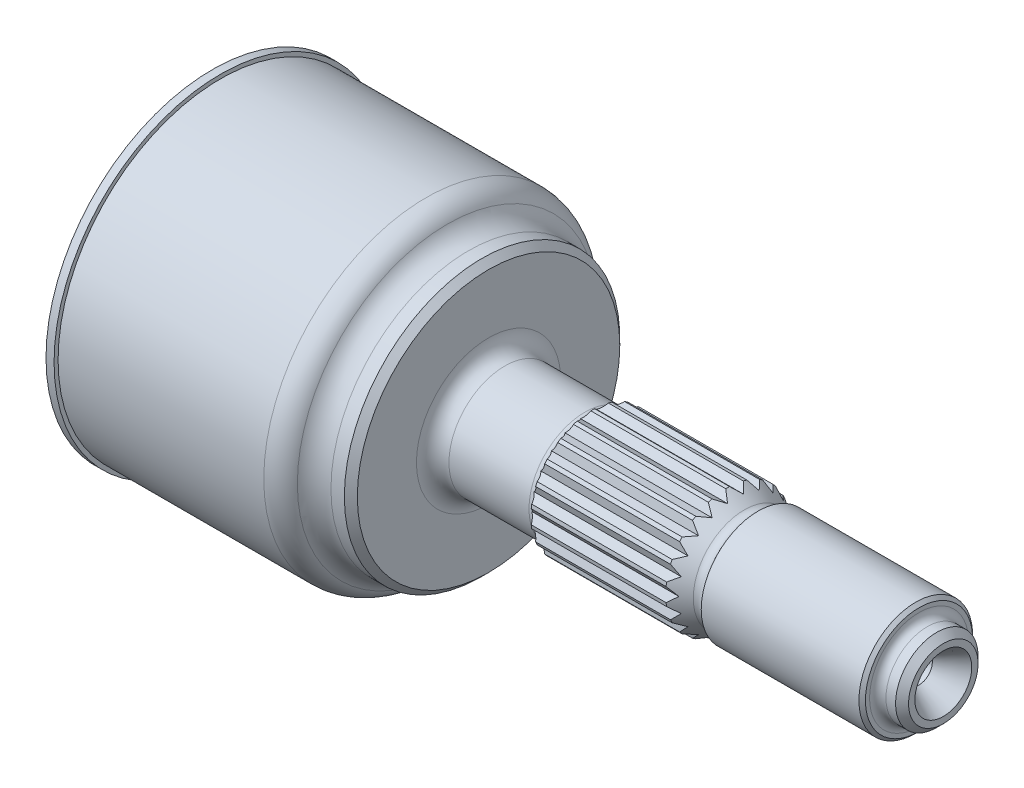
SolidWorks part; units mm, degrees
material "AISI 4340 Steel, normalized"
ref_plane "Front-XY" through (0, 0, 0) normal (0, 0, 1) x (1, 0, 0)
ref_plane "Top-XZ" through (0, 0, 0) normal (0, 1, 0) x (1, 0, 0)
ref_plane "Right-YZ" through (0, 0, 0) normal (1, 0, 0) x (0, 0, -1)
sketch "Sketch1" plane through (0, 0, 0) normal (0, 1, 0) x (1, 0, 0)
  line L0 (0, 0) -> (0, 32.5374)
  line L1 (0, 32.5374) -> (1.5748, 32.5374)
  line L2 (1.5748, 32.5374) -> (1.5748, 31.75)
  line L3 (1.5748, 31.75) -> (41.783, 31.75)
  line L4 (100.711, 12.1031) -> (103.9797, 9.9804)
  line L5 (50.0888, 26.924) -> (52.705, 26.924)
  line L6 (53.975, 25.654) -> (53.975, 14.097)
  line L7 (57.15, 10.922) -> (72.7964, 10.922)
  line L8 (74.3407, 12.1031) -> (100.711, 12.1031)
  line L9 (-31.2881, 0) -> (113.4065, 0) construction
  line L10 (52.705, 26.924) -> (53.975, 25.654)
  line L11 (106.6636, 11.1125) -> (106.1569, 10.3974)
  line L12 (106.6636, 11.1125) -> (137.4902, 11.1125)
  line L13 (138.1252, 10.4775) -> (138.1252, 9.6647)
  line L14 (139.7254, 8.0645) -> (141.605, 8.0645)
  line L15 (142.875, 6.7945) -> (142.875, 5.5626)
  line L16 (142.875, 5.5626) -> (138.1252, 2.6099)
  line L17 (138.1252, 2.6099) -> (134.3152, 2.6098)
  line L18 (134.3152, 2.6098) -> (132.5548, 0)
  line L19 (132.5548, 0) -> (0, 0)
  line L20 (141.605, 8.0645) -> (142.875, 6.7945)
  line L21 (137.4902, 11.1125) -> (138.1252, 10.4775)
  arc A0 (41.783, 31.75) -> (45.9359, 29.337) centre (41.783, 26.9698) cw
  arc A1 (45.9359, 29.337) -> (50.0888, 26.924) centre (50.0888, 31.7042) ccw
  arc A2 (53.975, 14.097) -> (57.15, 10.922) centre (57.15, 14.097) ccw
  arc A3 (72.7964, 10.922) -> (74.3407, 12.1031) centre (72.7964, 12.5222) ccw
  arc A4 (138.1252, 9.6647) -> (139.7254, 8.0645) centre (139.7254, 9.6647) ccw
  arc A5 (103.9797, 9.9804) -> (106.1569, 10.3974) centre (104.8512, 11.3224) ccw
  point P7 (53.975, 26.924)
  point P25 (138.1252, 11.1125)
  point P27 (142.875, 8.0645)
  point P35 (138.1252, 8.0645)
  dimension "D1" = 31.75
  dimension "D8" = 50.0888
  dimension "D10" = 3.175
  dimension "D11" = 1.6002
  dimension "D28" = 1.6002
  dimension "D16" = 1.6002
  dimension "D2" = 26.924
  dimension "D3" = 53.975
  dimension "D4" = 1.5748
  dimension "D5" = 32.5374
  dimension "D6" = 1.27
  dimension "D7" = 45
  dimension "D9" = 41.783
  dimension "D12" = 72.7964
  dimension "D13" = 10.922
  dimension "D14" = 12.1031
  dimension "D15" = 100.711
  dimension "D17" = 33
  dimension "D18" = 8.0645
  dimension "D19" = 142.875
  dimension "D20" = 138.1252
  dimension "D21" = 11.1125
  dimension "D22" = 5.5626
  dimension "D23" = 1.27
  dimension "D24" = 45
  dimension "D25" = 56
  dimension "D26" = 2.6098
  dimension "D27" = 3.81
  dimension "D29" = 104.8512
  dimension "D30" = 0.5067
revolve "ProfileRevolve" add sketch "Sketch1" angle 360 about L9
cosmetic thread "Cosmetic Thread1" parameters "D2"=19.304
sketch "Sketch2" plane through (0, 0, 0) normal (-1, 0, 0) x (0, 0, 1)
  circle A0 centre (0, 0) radius 18.2245
  dimension "D1" = 36.449
extrude "CenterPocket" cut sketch "Sketch2" against normal blind 43.942
sketch "Sketch4" plane through (0, 0, 0) normal (-1, 0, 0) x (0, 0, 1)
  circle A0 centre (0, 24.638) radius 4.7625
  circle A1 centre (21.3371, -12.319) radius 4.7625
  circle A2 centre (-21.3371, -12.319) radius 4.7625
  dimension "D1" = 9.525
  dimension "D2" = 24.638
extrude "Holes" cut sketch "Sketch4" against normal blind 41.275
sketch "Sketch5" plane through (0, 0, 0) normal (-1, 0, 0) x (0, 0, 1)
  arc A0 (-9.9429, -27.1954) -> (9.9429, -27.1954) centre (0, 0) ccw
  circle A1 centre (0, 0) radius 20.32 construction
  arc A2 (11.7591, -25.4916) -> (-11.7591, -25.4916) centre (0, -20.32) ccw
  arc A3 (-27.9559, 2.5622) -> (-16.1969, 22.9294) centre (-17.5976, 10.16) ccw
  arc A4 (-18.5804, 22.2085) -> (-28.5233, 4.9868) centre (0, 0) ccw
  arc A5 (16.1969, 22.9294) -> (27.9559, 2.5622) centre (17.5976, 10.16) ccw
  arc A6 (28.5233, 4.9868) -> (18.5804, 22.2085) centre (0, 0) ccw
  arc A7 (11.7591, -25.4916) -> (9.9429, -27.1954) centre (8.8527, -24.2134) cw
  arc A8 (-11.7591, -25.4916) -> (-9.9429, -27.1954) centre (-8.8527, -24.2134) ccw
  arc A9 (27.9559, 2.5622) -> (28.5233, 4.9868) centre (25.3958, 4.44) ccw
  arc A10 (16.1969, 22.9294) -> (18.5804, 22.2085) centre (16.5431, 19.7734) cw
  arc A11 (-16.1969, 22.9294) -> (-18.5804, 22.2085) centre (-16.5431, 19.7734) ccw
  arc A12 (-27.9559, 2.5622) -> (-28.5233, 4.9868) centre (-25.3958, 4.44) cw
  dimension "D1" = 57.912
  dimension "D2" = 40.64
  dimension "D3" = 25.6921
  dimension "D4" = 3.175
extrude "Extrude3" cut sketch "Sketch5" against normal blind 43.942
sketch "Sketch6" plane through (0, 0, 0) normal (0, 0, 1) x (1, 0, 0)
  line L0 (43.922, 18.2245) -> (2.9156, 18.2245)
  line L1 (-21.4392, 0) -> (31.2558, 0) construction
  line L3 (-4.0132, 0) -> (50.8508, 0)
  arc A0 (2.9156, 18.2245) -> (-4.0132, 0) centre (23.4188, 0) ccw
  arc A1 (50.8508, 0) -> (43.922, 18.2245) centre (23.4188, 0) ccw
  dimension "D1" = 54.864
  dimension "D2" = 23.4188
  dimension "D3" = 18.2245
revolve "Cut-Revolve1" cut sketch "Sketch6" angle 360 about L1
ref_plane "Plane1" through (72.7964, 0, 0) normal (1, 0, 0) x (0, 0, -1)
sketch "Sketch7" plane through (72.7964, 0, 0) normal (1, 0, 0) x (0, 0, -1)
  line L0 (0, 12.1031) -> (1.5771, 10.9692) construction
  line L1 (1.5771, 10.9692) -> (3.4098, 11.6128) construction
  line L2 (0.3686, 12.0975) -> (1.5771, 10.9692)
  line L3 (1.5771, 10.9692) -> (3.0546, 11.7113)
  line L4 (0, 12.1031) -> (0.3686, 12.0975) construction
  line L5 (3.0546, 11.7113) -> (3.4098, 11.6128) construction
  line L6 (3.7619, 11.5036) -> (4.6036, 10.0805)
  line L7 (4.6036, 10.0805) -> (6.2303, 10.3763)
  line L8 (6.8505, 9.9778) -> (7.2571, 8.3752)
  line L9 (7.2571, 8.3752) -> (8.9013, 8.2007)
  line L10 (9.384, 7.6436) -> (9.3227, 5.9914)
  line L11 (9.3227, 5.9914) -> (10.8512, 5.3607)
  line L12 (11.1574, 4.6902) -> (10.6331, 3.1221)
  line L13 (10.6331, 3.1221) -> (11.9219, 2.0865)
  line L14 (12.0268, 1.3568) -> (11.082, 0)
  line L15 (11.082, 0) -> (12.0268, -1.3568)
  line L16 (11.9219, -2.0865) -> (10.6331, -3.1221)
  line L17 (10.6331, -3.1221) -> (11.1574, -4.6902)
  line L18 (10.8512, -5.3607) -> (9.3227, -5.9914)
  line L19 (9.3227, -5.9914) -> (9.384, -7.6436)
  line L20 (8.9013, -8.2007) -> (7.2571, -8.3752)
  line L21 (7.2571, -8.3752) -> (6.8505, -9.9778)
  line L22 (6.2303, -10.3763) -> (4.6036, -10.0805)
  line L23 (4.6036, -10.0805) -> (3.7619, -11.5036)
  line L24 (3.0546, -11.7113) -> (1.5771, -10.9692)
  line L25 (1.5771, -10.9692) -> (0.3686, -12.0975)
  line L26 (-0.3686, -12.0975) -> (-1.5771, -10.9692)
  line L27 (-1.5771, -10.9692) -> (-3.0546, -11.7113)
  line L28 (-3.7619, -11.5036) -> (-4.6036, -10.0805)
  line L29 (-4.6036, -10.0805) -> (-6.2303, -10.3763)
  line L30 (-6.8505, -9.9778) -> (-7.2571, -8.3752)
  line L31 (-7.2571, -8.3752) -> (-8.9013, -8.2007)
  line L32 (-9.384, -7.6436) -> (-9.3227, -5.9914)
  line L33 (-9.3227, -5.9914) -> (-10.8512, -5.3607)
  line L34 (-11.1574, -4.6902) -> (-10.6331, -3.1221)
  line L35 (-10.6331, -3.1221) -> (-11.9219, -2.0865)
  line L36 (-12.0268, -1.3568) -> (-11.082, 0)
  line L37 (-11.082, 0) -> (-12.0268, 1.3568)
  line L38 (-11.9219, 2.0865) -> (-10.6331, 3.1221)
  line L39 (-10.6331, 3.1221) -> (-11.1574, 4.6902)
  line L40 (-10.8512, 5.3607) -> (-9.3227, 5.9914)
  line L41 (-9.3227, 5.9914) -> (-9.384, 7.6436)
  line L42 (-8.9013, 8.2007) -> (-7.2571, 8.3752)
  line L43 (-7.2571, 8.3752) -> (-6.8505, 9.9778)
  line L44 (-6.2303, 10.3763) -> (-4.6036, 10.0805)
  line L45 (-4.6036, 10.0805) -> (-3.7619, 11.5036)
  line L46 (-3.0546, 11.7113) -> (-1.5771, 10.9692)
  line L47 (-1.5771, 10.9692) -> (-0.3686, 12.0975)
  circle A1 centre (0, 0) radius 12.1031 construction
  arc A2 (3.0546, 11.7113) -> (0.3686, 12.0975) centre (0, 0) ccw
  arc A3 (6.2303, 10.3763) -> (3.7619, 11.5036) centre (0, 0) ccw
  arc A4 (8.9013, 8.2007) -> (6.8505, 9.9778) centre (0, 0) ccw
  arc A5 (10.8512, 5.3607) -> (9.384, 7.6436) centre (0, 0) ccw
  arc A6 (11.9219, 2.0865) -> (11.1574, 4.6902) centre (0, 0) ccw
  arc A7 (12.0268, -1.3568) -> (12.0268, 1.3568) centre (0, 0) ccw
  arc A8 (11.1574, -4.6902) -> (11.9219, -2.0865) centre (0, 0) ccw
  arc A9 (9.384, -7.6436) -> (10.8512, -5.3607) centre (0, 0) ccw
  arc A10 (6.8505, -9.9778) -> (8.9013, -8.2007) centre (0, 0) ccw
  arc A11 (3.7619, -11.5036) -> (6.2303, -10.3763) centre (0, 0) ccw
  arc A12 (0.3686, -12.0975) -> (3.0546, -11.7113) centre (0, 0) ccw
  arc A13 (-3.0546, -11.7113) -> (-0.3686, -12.0975) centre (0, 0) ccw
  arc A14 (-6.2303, -10.3763) -> (-3.7619, -11.5036) centre (0, 0) ccw
  arc A15 (-8.9013, -8.2007) -> (-6.8505, -9.9778) centre (0, 0) ccw
  arc A16 (-10.8512, -5.3607) -> (-9.384, -7.6436) centre (0, 0) ccw
  arc A17 (-11.9219, -2.0865) -> (-11.1574, -4.6902) centre (0, 0) ccw
  arc A18 (-12.0268, 1.3568) -> (-12.0268, -1.3568) centre (0, 0) ccw
  arc A19 (-11.1574, 4.6902) -> (-11.9219, 2.0865) centre (0, 0) ccw
  arc A20 (-9.384, 7.6436) -> (-10.8512, 5.3607) centre (0, 0) ccw
  arc A21 (-6.8505, 9.9778) -> (-8.9013, 8.2007) centre (0, 0) ccw
  arc A22 (-3.7619, 11.5036) -> (-6.2303, 10.3763) centre (0, 0) ccw
  arc A23 (-0.3686, 12.0975) -> (-3.0546, 11.7113) centre (0, 0) ccw
  point P0 (-11.0094, 5.0278)
  point P1 (-11.9799, 1.7225)
  point P3 (0, 12.1031)
  point P8 (6.5434, -10.1818)
  point P9 (3.4098, 11.6128)
  point P10 (-11.9799, -1.7225)
  point P11 (6.5434, 10.1818)
  point P12 (9.1469, 7.9258)
  point P13 (11.0094, 5.0278)
  point P14 (11.9799, 1.7225)
  point P15 (11.9799, -1.7225)
  point P16 (11.0094, -5.0278)
  point P17 (9.1469, -7.9258)
  point P18 (-3.4098, 11.6128)
  point P19 (3.4098, -11.6128)
  point P20 (0, -12.1031)
  point P21 (-3.4098, -11.6128)
  point P22 (-6.5434, -10.1818)
  point P23 (-9.1469, -7.9258)
  point P24 (-11.0094, -5.0278)
  point P25 (-6.5434, 10.1818)
  point P26 (-9.1469, 7.9258)
  dimension "D1" = 0.3686
  dimension "D2" = 3.4098
extrude "Extrude4" cut sketch "Sketch7" along normal up to next
sketch "Sketch10" plane through (0, 0, 0) normal (0, 1, 0) x (1, 0, 0)
  line L0 (106.6636, 11.1125) -> (107.4335, 9.779)
  line L1 (0, 0) -> (202.1127, 0) construction
  line L2 (106.6636, -11.1125) -> (106.6636, 11.1125) construction
  line L3 (107.4335, 9.779) -> (108.2034, 11.1125)
  line L4 (137.4902, 11.1125) -> (106.6636, 11.1125) construction
  line L5 (108.2034, 11.1125) -> (106.6636, 11.1125)
  line L6 (109.2478, 9.779) -> (110.0177, 11.1125)
  line L7 (110.0177, 11.1125) -> (108.4779, 11.1125)
  line L8 (108.4779, 11.1125) -> (109.2478, 9.779)
  line L9 (111.062, 9.779) -> (111.8319, 11.1125)
  line L10 (111.8319, 11.1125) -> (110.2921, 11.1125)
  line L11 (110.2921, 11.1125) -> (111.062, 9.779)
  line L12 (112.8763, 9.779) -> (113.6462, 11.1125)
  line L13 (113.6462, 11.1125) -> (112.1064, 11.1125)
  line L14 (112.1064, 11.1125) -> (112.8763, 9.779)
  line L15 (114.6906, 9.779) -> (115.4605, 11.1125)
  line L16 (115.4605, 11.1125) -> (113.9207, 11.1125)
  line L17 (113.9207, 11.1125) -> (114.6906, 9.779)
  line L18 (116.5049, 9.779) -> (117.2748, 11.1125)
  line L19 (117.2748, 11.1125) -> (115.735, 11.1125)
  line L20 (115.735, 11.1125) -> (116.5049, 9.779)
  line L21 (118.3192, 9.779) -> (119.0891, 11.1125)
  line L22 (119.0891, 11.1125) -> (117.5493, 11.1125)
  line L23 (117.5493, 11.1125) -> (118.3192, 9.779)
  line L24 (120.1335, 9.779) -> (120.9034, 11.1125)
  line L25 (120.9034, 11.1125) -> (119.3636, 11.1125)
  line L26 (119.3636, 11.1125) -> (120.1335, 9.779)
  line L27 (121.9478, 9.779) -> (122.7177, 11.1125)
  line L28 (122.7177, 11.1125) -> (121.1779, 11.1125)
  line L29 (121.1779, 11.1125) -> (121.9478, 9.779)
  line L30 (123.762, 9.779) -> (124.5319, 11.1125)
  line L31 (124.5319, 11.1125) -> (122.9921, 11.1125)
  line L32 (122.9921, 11.1125) -> (123.762, 9.779)
  line L33 (125.5763, 9.779) -> (126.3462, 11.1125)
  line L34 (126.3462, 11.1125) -> (124.8064, 11.1125)
  line L35 (124.8064, 11.1125) -> (125.5763, 9.779)
  line L36 (127.3906, 9.779) -> (128.1605, 11.1125)
  line L37 (128.1605, 11.1125) -> (126.6207, 11.1125)
  line L38 (126.6207, 11.1125) -> (127.3906, 9.779)
  line L39 (129.2049, 9.779) -> (129.9748, 11.1125)
  line L40 (129.9748, 11.1125) -> (128.435, 11.1125)
  line L41 (128.435, 11.1125) -> (129.2049, 9.779)
  line L42 (131.0192, 9.779) -> (131.7891, 11.1125)
  line L43 (131.7891, 11.1125) -> (130.2493, 11.1125)
  line L44 (130.2493, 11.1125) -> (131.0192, 9.779)
  line L45 (132.8335, 9.779) -> (133.6034, 11.1125)
  line L46 (133.6034, 11.1125) -> (132.0636, 11.1125)
  line L47 (132.0636, 11.1125) -> (132.8335, 9.779)
  line L48 (134.6478, 9.779) -> (135.4177, 11.1125)
  line L49 (135.4177, 11.1125) -> (133.8779, 11.1125)
  line L50 (133.8779, 11.1125) -> (134.6478, 9.779)
  line L51 (136.462, 9.779) -> (137.2319, 11.1125)
  line L52 (137.2319, 11.1125) -> (135.6921, 11.1125)
  line L53 (135.6921, 11.1125) -> (136.462, 9.779)
  line L54 (138.2763, 9.779) -> (139.0462, 11.1125)
  line L55 (139.0462, 11.1125) -> (137.5064, 11.1125)
  line L56 (137.5064, 11.1125) -> (138.2763, 9.779)
  dimension "D1" = 9.779
  dimension "D2" = 30
  dimension "D3" = 60
revolve "Cut-Revolve2" [suppressed] cut sketch "Sketch10" angle 360 about L1
sketch "Sketch11" [suppressed] plane through (0, 0, 0) normal (0, 1, 0) x (1, 0, 0)
  line L0 (142.875, 0) -> (158.4234, 0) construction
  line L2 (131.0192, 5.5626) -> (131.0192, 6.7945)
  line L4 (131.0192, 6.7945) -> (129.7492, 8.0645)
  line L5 (129.7492, 8.0645) -> (127.8696, 8.0645)
  line L6 (141.605, 8.0645) -> (139.7254, 8.0645) construction
  line L8 (142.875, 6.7945) -> (141.605, 8.0645) construction
  line L9 (142.875, 6.7945) -> (141.605, 8.0645) construction
  line L11 (142.875, -6.7945) -> (142.875, 6.7945) construction
  line L12 (131.0192, -9.779) -> (131.0192, 9.779) construction
  line L14 (126.2694, 9.6647) -> (126.2694, 11.1125)
  line L15 (126.2694, 11.1125) -> (142.875, 11.1125)
  line L16 (142.875, 11.1125) -> (142.875, 0)
  line L17 (131.0192, 5.5626) -> (127.8696, 2.667)
  line L18 (141.605, 8.0645) -> (139.7254, 8.0645) construction
  line L20 (127.8696, 2.667) -> (124.5319, 2.667)
  line L21 (124.5319, 2.667) -> (123.4272, 0)
  line L23 (124.5319, -11.1125) -> (124.5319, 11.1125) construction
  line L24 (123.4272, 0) -> (142.875, 0)
  line L25 (133.8779, 11.1125) -> (133.6034, 11.1125) construction
  arc A1 (127.8696, 8.0645) -> (126.2694, 9.6647) centre (127.8696, 9.6647) cw
  dimension "D1" = 1.6002
  dimension "D2" = 5.5626
  dimension "D3" = 2.667
  dimension "D4" = 67.5
revolve "Cut-Revolve3" [suppressed] cut sketch "Sketch11" angle 360 about L0
sketch "Sketch13" plane through (0, 0, 0) normal (-1, 0, 0) x (0, 0, 1)
  circle A0 centre (0, 0) radius 38.1
  arc A1 (8.5595, 23.8472) -> (0.9863, 21.7582) centre (1.5614, 34.4451) cw
  arc A2 (-0.9863, 21.7582) -> (-8.5595, 23.8472) centre (-1.5614, 34.4451) cw
  arc A3 (24.9321, -4.5108) -> (19.3363, -10.0249) centre (30.611, -15.8704) ccw
  arc A4 (18.35, -11.7332) -> (16.3725, -19.3364) centre (29.0497, -18.5748) ccw
  arc A5 (-16.3725, -19.3364) -> (-18.35, -11.7332) centre (-29.0497, -18.5748) ccw
  arc A6 (-19.3363, -10.0249) -> (-24.9321, -4.5108) centre (-30.611, -15.8704) ccw
  arc A216 (15.8091, 26.4642) -> (5.3816, 21.1052) centre (17.5976, 10.16) ccw
  arc A217 (20.8622, 24.9359) -> (15.8091, 26.4642) centre (16.5431, 19.7734) ccw
  arc A218 (32.0262, 5.5993) -> (20.8622, 24.9359) centre (0, 0) ccw
  arc A219 (30.8233, 0.459) -> (32.0262, 5.5993) centre (25.3958, 4.44) ccw
  arc A220 (20.9684, -5.8919) -> (30.8233, 0.459) centre (17.5976, 10.16) ccw
  arc A221 (15.5868, -15.2132) -> (20.9684, -5.8919) centre (0, 0) ccw
  arc A222 (15.0142, -26.9232) -> (15.5868, -15.2132) centre (0, -20.32) ccw
  arc A223 (11.164, -30.5351) -> (15.0142, -26.9232) centre (8.8527, -24.2134) ccw
  arc A224 (-11.164, -30.5351) -> (11.164, -30.5351) centre (0, 0) ccw
  arc A225 (-15.0142, -26.9232) -> (-11.164, -30.5351) centre (-8.8527, -24.2134) ccw
  arc A226 (-15.5868, -15.2132) -> (-15.0142, -26.9232) centre (0, -20.32) ccw
  arc A227 (5.3816, 21.1052) -> (-5.3816, 21.1052) centre (0, 0) ccw
  arc A228 (-20.9684, -5.8919) -> (-15.5868, -15.2132) centre (0, 0) ccw
  arc A229 (-30.8233, 0.459) -> (-20.9684, -5.8919) centre (-17.5976, 10.16) ccw
  arc A230 (-32.0262, 5.5993) -> (-30.8233, 0.459) centre (-25.3958, 4.44) ccw
  arc A231 (-20.8622, 24.9359) -> (-32.0262, 5.5993) centre (0, 0) ccw
  arc A232 (-15.8091, 26.4642) -> (-20.8622, 24.9359) centre (-16.5431, 19.7734) ccw
  arc A233 (-5.3816, 21.1052) -> (-15.8091, 26.4642) centre (-17.5976, 10.16) ccw
  arc A234 (15.8091, 26.4642) -> (8.5595, 23.8472) centre (17.5976, 10.16) ccw
  arc A235 (20.8622, 24.9359) -> (15.8091, 26.4642) centre (16.5431, 19.7734) ccw
  arc A236 (32.0262, 5.5993) -> (20.8622, 24.9359) centre (0, 0) ccw
  arc A237 (30.8233, 0.459) -> (32.0262, 5.5993) centre (25.3958, 4.44) ccw
  arc A238 (24.9321, -4.5108) -> (30.8233, 0.459) centre (17.5976, 10.16) ccw
  arc A239 (18.35, -11.7332) -> (19.3363, -10.0249) centre (0, 0) ccw
  arc A240 (15.0142, -26.9232) -> (16.3725, -19.3364) centre (0, -20.32) ccw
  arc A241 (11.164, -30.5351) -> (15.0142, -26.9232) centre (8.8527, -24.2134) ccw
  arc A242 (-11.164, -30.5351) -> (11.164, -30.5351) centre (0, 0) ccw
  arc A243 (-15.0142, -26.9232) -> (-11.164, -30.5351) centre (-8.8527, -24.2134) ccw
  arc A244 (-16.3725, -19.3364) -> (-15.0142, -26.9232) centre (0, -20.32) ccw
  arc A245 (0.9863, 21.7582) -> (-0.9863, 21.7582) centre (0, 0) ccw
  arc A246 (-19.3363, -10.0249) -> (-18.35, -11.7332) centre (0, 0) ccw
  arc A247 (-30.8233, 0.459) -> (-24.9321, -4.5108) centre (-17.5976, 10.16) ccw
  arc A248 (-32.0262, 5.5993) -> (-30.8233, 0.459) centre (-25.3958, 4.44) ccw
  arc A249 (-20.8622, 24.9359) -> (-32.0262, 5.5993) centre (0, 0) ccw
  arc A250 (-15.8091, 26.4642) -> (-20.8622, 24.9359) centre (-16.5431, 19.7734) ccw
  arc A251 (-8.5595, 23.8472) -> (-15.8091, 26.4642) centre (-17.5976, 10.16) ccw
  dimension "D2" = 76.2
  dimension "D3" = 12.7
  dimension "D1" = 3.556
extrude "Extrude6" [suppressed] cut sketch "Sketch13" against normal up to next
sketch3d "3DSketch1"
  point P0 (0, 0, 0)
ref_axis "Axis1" through (41.783, 0, 0) along (-1, 0, 0)
